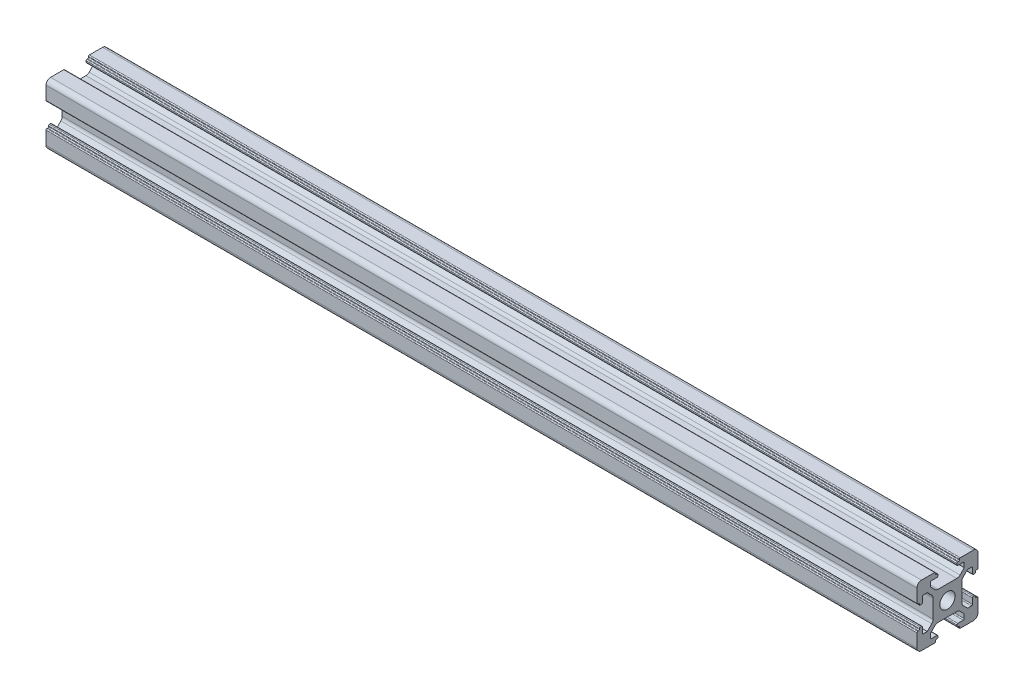
SolidWorks part; units mm, degrees
ref_plane "Front Plane" through (0, 0, 0) normal (0, 0, 1) x (1, 0, 0)
ref_plane "Top Plane" through (0, 0, 0) normal (0, 1, 0) x (1, 0, 0)
ref_plane "Right Plane" through (0, 0, 0) normal (1, 0, 0) x (0, 0, -1)
sketch "Sketch1" plane through (0, 0, 0) normal (1, 0, 0) x (0, 0, -1)
  line L0 (0, 0) -> (0, 50000) construction
  line L1 (0, 0) -> (-50000, 0) construction
  line L2 (10, 4.2) -> (10, 8.5)
  line L3 (9.7, 3.9) -> (9.5, 3.9)
  line L4 (9.2, 3.6) -> (9.2, 3.4)
  line L5 (8.9, 3.1) -> (8.5, 3.1)
  line L6 (8.2, 3.4) -> (8.2, 5.2)
  line L7 (7.9, 5.5) -> (6.6, 5.5)
  line L8 (6.6, 5.5) -> (5.1393, 4.0393)
  line L9 (8.5, 10) -> (4.2, 10)
  line L10 (3.9, 9.7) -> (3.9, 9.5)
  line L11 (3.6, 9.2) -> (3.4, 9.2)
  line L12 (3.1, 8.9) -> (3.1, 8.5)
  line L13 (3.4, 8.2) -> (5.2, 8.2)
  line L14 (5.5, 7.9) -> (5.5, 6.5213)
  line L15 (5.5, 6.5213) -> (4.118, 5.1393)
  line L16 (4.7, 2.9787) -> (4.7, -2.9787)
  line L17 (3.0574, 4.7) -> (-3.0574, 4.7)
  line L18 (-4.7, 2.9787) -> (-4.7, -2.9787)
  line L19 (-5.5, 6.5213) -> (-4.118, 5.1393)
  line L20 (-5.5, 7.9) -> (-5.5, 6.5213)
  line L21 (-3.4, 8.2) -> (-5.2, 8.2)
  line L22 (-3.1, 8.9) -> (-3.1, 8.5)
  line L23 (-3.6, 9.2) -> (-3.4, 9.2)
  line L24 (-3.9, 9.7) -> (-3.9, 9.5)
  line L25 (-8.5, 10) -> (-4.2, 10)
  line L26 (-6.6, 5.5) -> (-5.1393, 4.0393)
  line L27 (-7.9, 5.5) -> (-6.6, 5.5)
  line L28 (-8.2, 3.4) -> (-8.2, 5.2)
  line L29 (-8.9, 3.1) -> (-8.5, 3.1)
  line L30 (-9.2, 3.6) -> (-9.2, 3.4)
  line L31 (-9.7, 3.9) -> (-9.5, 3.9)
  line L32 (-10, 4.2) -> (-10, 8.5)
  line L33 (-10, -4.2) -> (-10, -8.5)
  line L34 (-9.7, -3.9) -> (-9.5, -3.9)
  line L35 (-9.2, -3.6) -> (-9.2, -3.4)
  line L36 (-8.9, -3.1) -> (-8.5, -3.1)
  line L37 (-8.2, -3.4) -> (-8.2, -5.2)
  line L38 (-7.9, -5.5) -> (-6.6, -5.5)
  line L39 (-6.6, -5.5) -> (-5.1393, -4.0393)
  line L40 (-8.5, -10) -> (-4.2, -10)
  line L41 (-3.9, -9.7) -> (-3.9, -9.5)
  line L42 (-3.6, -9.2) -> (-3.4, -9.2)
  line L43 (-3.1, -8.9) -> (-3.1, -8.5)
  line L44 (-3.4, -8.2) -> (-5.2, -8.2)
  line L45 (-5.5, -7.9) -> (-5.5, -6.5213)
  line L46 (-5.5, -6.5213) -> (-4.118, -5.1393)
  line L47 (3.0574, -4.7) -> (-3.0574, -4.7)
  line L48 (5.5, -6.5213) -> (4.118, -5.1393)
  line L49 (5.5, -7.9) -> (5.5, -6.5213)
  line L50 (3.4, -8.2) -> (5.2, -8.2)
  line L51 (3.1, -8.9) -> (3.1, -8.5)
  line L52 (3.6, -9.2) -> (3.4, -9.2)
  line L53 (3.9, -9.7) -> (3.9, -9.5)
  line L54 (8.5, -10) -> (4.2, -10)
  line L55 (6.6, -5.5) -> (5.1393, -4.0393)
  line L56 (7.9, -5.5) -> (6.6, -5.5)
  line L57 (8.2, -3.4) -> (8.2, -5.2)
  line L58 (8.9, -3.1) -> (8.5, -3.1)
  line L59 (9.2, -3.6) -> (9.2, -3.4)
  line L60 (9.7, -3.9) -> (9.5, -3.9)
  line L61 (10, -4.2) -> (10, -8.5)
  circle A0 centre (0, 0) radius 2.5
  arc A1 (10, 8.5) -> (8.5, 10) centre (8.5, 8.5) ccw
  arc A2 (9.7, 3.9) -> (10, 4.2) centre (9.7, 4.2) ccw
  arc A3 (9.5, 3.9) -> (9.2, 3.6) centre (9.5, 3.6) ccw
  arc A4 (9.2, 3.4) -> (8.9, 3.1) centre (8.9, 3.4) cw
  arc A5 (8.5, 3.1) -> (8.2, 3.4) centre (8.5, 3.4) cw
  arc A6 (8.2, 5.2) -> (7.9, 5.5) centre (7.9, 5.2) ccw
  arc A7 (5.2, 8.2) -> (5.5, 7.9) centre (5.2, 7.9) cw
  arc A8 (3.1, 8.5) -> (3.4, 8.2) centre (3.4, 8.5) ccw
  arc A9 (3.4, 9.2) -> (3.1, 8.9) centre (3.4, 8.9) ccw
  arc A10 (4.2, 10) -> (3.9, 9.7) centre (4.2, 9.7) ccw
  arc A11 (3.9, 9.5) -> (3.6, 9.2) centre (3.6, 9.5) cw
  arc A12 (4.7, 2.9787) -> (5.1393, 4.0393) centre (6.2, 2.9787) cw
  arc A13 (3.0574, 4.7) -> (4.118, 5.1393) centre (3.0574, 6.2) ccw
  arc A14 (-3.0574, 4.7) -> (-4.118, 5.1393) centre (-3.0574, 6.2) cw
  arc A15 (-4.7, 2.9787) -> (-5.1393, 4.0393) centre (-6.2, 2.9787) ccw
  arc A16 (-3.9, 9.5) -> (-3.6, 9.2) centre (-3.6, 9.5) ccw
  arc A17 (-4.2, 10) -> (-3.9, 9.7) centre (-4.2, 9.7) cw
  arc A18 (-3.4, 9.2) -> (-3.1, 8.9) centre (-3.4, 8.9) cw
  arc A19 (-3.1, 8.5) -> (-3.4, 8.2) centre (-3.4, 8.5) cw
  arc A20 (-5.2, 8.2) -> (-5.5, 7.9) centre (-5.2, 7.9) ccw
  arc A21 (-8.2, 5.2) -> (-7.9, 5.5) centre (-7.9, 5.2) cw
  arc A22 (-8.5, 3.1) -> (-8.2, 3.4) centre (-8.5, 3.4) ccw
  arc A23 (-9.2, 3.4) -> (-8.9, 3.1) centre (-8.9, 3.4) ccw
  arc A24 (-9.5, 3.9) -> (-9.2, 3.6) centre (-9.5, 3.6) cw
  arc A25 (-9.7, 3.9) -> (-10, 4.2) centre (-9.7, 4.2) cw
  arc A26 (-10, 8.5) -> (-8.5, 10) centre (-8.5, 8.5) cw
  arc A27 (-10, -8.5) -> (-8.5, -10) centre (-8.5, -8.5) ccw
  arc A28 (-9.7, -3.9) -> (-10, -4.2) centre (-9.7, -4.2) ccw
  arc A29 (-9.5, -3.9) -> (-9.2, -3.6) centre (-9.5, -3.6) ccw
  arc A30 (-9.2, -3.4) -> (-8.9, -3.1) centre (-8.9, -3.4) cw
  arc A31 (-8.5, -3.1) -> (-8.2, -3.4) centre (-8.5, -3.4) cw
  arc A32 (-8.2, -5.2) -> (-7.9, -5.5) centre (-7.9, -5.2) ccw
  arc A33 (-5.2, -8.2) -> (-5.5, -7.9) centre (-5.2, -7.9) cw
  arc A34 (-3.1, -8.5) -> (-3.4, -8.2) centre (-3.4, -8.5) ccw
  arc A35 (-3.4, -9.2) -> (-3.1, -8.9) centre (-3.4, -8.9) ccw
  arc A36 (-4.2, -10) -> (-3.9, -9.7) centre (-4.2, -9.7) ccw
  arc A37 (-3.9, -9.5) -> (-3.6, -9.2) centre (-3.6, -9.5) cw
  arc A38 (-4.7, -2.9787) -> (-5.1393, -4.0393) centre (-6.2, -2.9787) cw
  arc A39 (-3.0574, -4.7) -> (-4.118, -5.1393) centre (-3.0574, -6.2) ccw
  arc A40 (3.0574, -4.7) -> (4.118, -5.1393) centre (3.0574, -6.2) cw
  arc A41 (4.7, -2.9787) -> (5.1393, -4.0393) centre (6.2, -2.9787) ccw
  arc A42 (3.9, -9.5) -> (3.6, -9.2) centre (3.6, -9.5) ccw
  arc A43 (4.2, -10) -> (3.9, -9.7) centre (4.2, -9.7) cw
  arc A44 (3.4, -9.2) -> (3.1, -8.9) centre (3.4, -8.9) cw
  arc A45 (3.1, -8.5) -> (3.4, -8.2) centre (3.4, -8.5) cw
  arc A46 (5.2, -8.2) -> (5.5, -7.9) centre (5.2, -7.9) ccw
  arc A47 (8.2, -5.2) -> (7.9, -5.5) centre (7.9, -5.2) cw
  arc A48 (8.5, -3.1) -> (8.2, -3.4) centre (8.5, -3.4) ccw
  arc A49 (9.2, -3.4) -> (8.9, -3.1) centre (8.9, -3.4) ccw
  arc A50 (9.5, -3.9) -> (9.2, -3.6) centre (9.5, -3.6) cw
  arc A51 (9.7, -3.9) -> (10, -4.2) centre (9.7, -4.2) cw
  arc A52 (10, -8.5) -> (8.5, -10) centre (8.5, -8.5) cw
  point P24 (10, 10)
  point P41 (3.1, 9.2)
  point P44 (3.9, 10)
  point P94 (4.7, 0)
  point P95 (0, 4.7)
  point P175 (0, -4.7)
  point P176 (-4.7, 0)
  dimension "D1" = 5
  dimension "D15" = 1.5
  dimension "D16" = 0.3
  dimension "D19" = 1.5
  dimension "D2" = 20
  dimension "D3" = 1.8
  dimension "D4" = 6.2
  dimension "D5" = 3.4
  dimension "D6" = 11
  dimension "D7" = 6.1
  dimension "D8" = 1.5
  dimension "D9" = 20
  dimension "D10" = 6.1
  dimension "D11" = 6.2
  dimension "D12" = 11
  dimension "D13" = 45
  dimension "D14" = 1.8
  dimension "D17" = 3.5
  dimension "D18" = 3.5
extrude "Boss-Extrude2" add sketch "Sketch1" along normal mid plane 285
